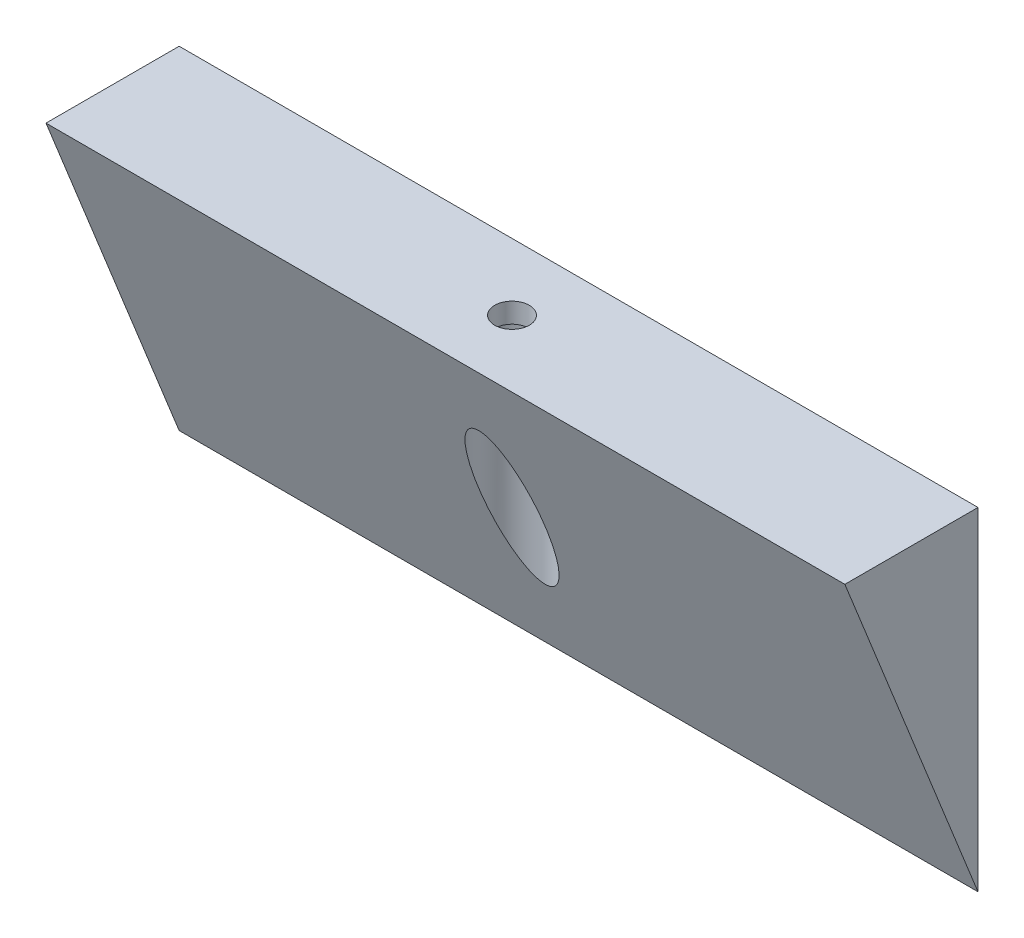
SolidWorks part; units mm, degrees
ref_plane "前视基准面" through (0, 0, 0) normal (0, 0, 1) x (1, 0, 0)
ref_plane "上视基准面" through (0, 0, 0) normal (0, 1, 0) x (1, 0, 0)
ref_plane "右视基准面" through (0, 0, 0) normal (1, 0, 0) x (0, 0, -1)
other "Configuration Table"
sketch "草图1" plane through (0, 0, 0) normal (0, 1, 0) x (1, 0, 0)
  line L1 (0, 0) -> (120, 0)
  line L2 (0, 0) -> (0, 20)
  line L3 (0, 20) -> (120, 20)
  line L4 (120, 0) -> (120, 20)
extrude "凸台-拉伸1" add sketch "草图1" along normal blind 50
sketch "草图2" plane through (0, 0, 0) normal (0, 0, 1) x (1, 0, 0)
  line L1 (0, 0) -> (6, 0)
  line L2 (0, 0) -> (0, -20)
  line L3 (0, -20) -> (6, -20)
  line L4 (6, 0) -> (6, -20)
extrude "凸台-拉伸2" add sketch "草图2" against normal blind 20
sketch "草图3" plane through (120, 0, 0) normal (1, 0, 0) x (0, 0, -1)
  line L0 (0, 50) -> (20, 0)
  line L1 (20, 0) -> (0, 0)
  line L2 (0, 0) -> (0, 50)
extrude "切除-拉伸1" cut sketch "草图3" against normal blind 114 contours L2 L0 L1
sketch "草图4" plane through (6, 0, 0) normal (1, 0, 0) x (0, 0, -1)
  line L4 (20, 0) -> (0, 0)
  line L5 (20, 0) -> (20, -20)
  line L6 (20, -20) -> (0, -20)
  line L7 (0, 0) -> (0, -20)
  circle A0 centre (10, 10) radius 2.6
extrude "切除-拉伸2" cut sketch "草图4" against normal blind 114 contours A0 | L5 L4 L7 L6
sketch "草图5" plane through (6, 0, 0) normal (1, 0, 0) x (0, 0, -1)
  circle A0 centre (10, 10) radius 5
extrude "切除-拉伸3" cut sketch "草图5" against normal blind 3
sketch "草图6" plane through (0, 50, 0) normal (0, 1, 0) x (1, 0, 0)
  line L0 (60, 20) -> (60, 0)
  line L1 (120, 20) -> (0, 20) construction
  line L2 (6, 0) -> (120, 0) construction
  circle A0 centre (60, 10) radius 2.6
extrude "切除-拉伸4" cut sketch "草图6" against normal blind 300 contours L0 A0 | L0 A0 region at (61.1035, 50, -10) region at (58.8965, 50, -10)
sketch "草图8" plane through (0, 50, 0) normal (0, 1, 0) x (1, 0, 0)
  circle A0 centre (60, 10) radius 5
extrude "切除-拉伸5" cut sketch "草图8" against normal blind 300
sketch "草图9" plane through (0, 50, 0) normal (0, 1, 0) x (1, 0, 0)
  circle A0 centre (60, 10) radius 5
  circle A1 centre (60, 10) radius 2.6
extrude "凸台-拉伸3" add sketch "草图9" against normal blind 3
mirror "镜向2" about plane through (120, 50, 0) normal (-1, 0, 0) of "切除-拉伸1", "切除-拉伸5", "凸台-拉伸1", "凸台-拉伸2", "切除-拉伸2", "切除-拉伸3", "凸台-拉伸3"
sketch "草图11" plane through (0, 50, 0) normal (0, 1, 0) x (1, 0, 0)
  line L0 (6, 0) -> (234, 0) construction
  line L1 (0, 20) -> (120, 20)
  line L2 (0, 20) -> (0, 0)
  line L3 (0, 0) -> (120, 0)
  line L4 (120, 20) -> (120, 0)
extrude "切除-拉伸6" cut sketch "草图11" against normal blind 100
sketch "草图12" plane through (234, 0, 0) normal (-1, 0, 0) x (0, 0, 1)
  line L0 (-20, 0) -> (0, 0)
  line L1 (0, 0) -> (0, 50)
  line L2 (0, 50) -> (-20, 0)
extrude "切除-拉伸7" cut sketch "草图12" against normal blind 10
